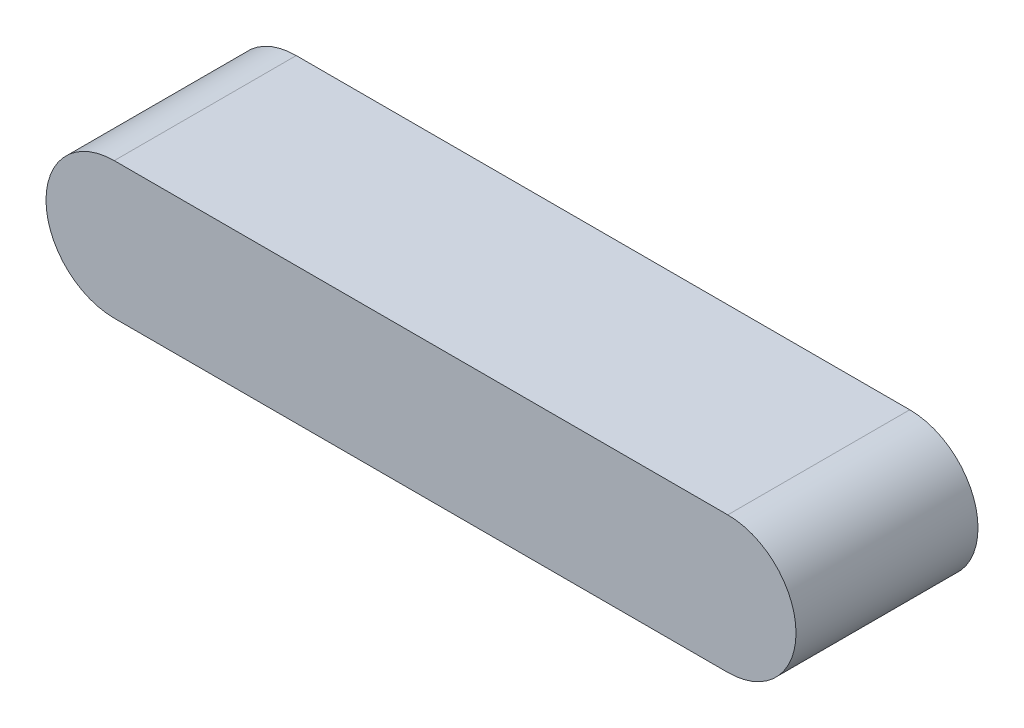
SolidWorks part; units mm, degrees
ref_plane "前视基准面" through (0, 0, 0) normal (0, 0, 1) x (1, 0, 0)
ref_plane "上视基准面" through (0, 0, 0) normal (0, 1, 0) x (1, 0, 0)
ref_plane "右视基准面" through (0, 0, 0) normal (1, 0, 0) x (0, 0, -1)
sketch "草图1" plane through (0, 0, 0) normal (0, 0, 1) x (1, 0, 0)
  line L0 (-64.7, 0) -> (70.15, 0) construction
  line L1 (-64.7, 15) -> (70.15, 15)
  line L2 (-64.7, -15) -> (70.15, -15)
  arc A0 (-64.7, 15) -> (-64.7, -15) centre (-64.7, 0) ccw
  arc A1 (70.15, -15) -> (70.15, 15) centre (70.15, 0) ccw
  point P3 (2.725, 0)
  point P8 (-79.7, 0)
  point P9 (85.15, 0)
  dimension "D1" = 164.85
  dimension "D2" = 30
  dimension "D3" = 64.7
extrude "凸台-拉伸1" add sketch "草图1" along normal blind 40
sketch "草图2" plane through (0, 0, 0) normal (0, 0, -1) x (-1, 0, 0)
  circle A0 centre (-37.5, 0) radius 7.25
  dimension "D1" = 14.5
  dimension "D2" = 37.5
extrude "切除-拉伸1" cut sketch "草图2" against normal blind 1
chamfer "倒角1" distance 0.5 angle 45 2 edges at (30.25, 0, 0) (30.25, 0, 1)
sketch "草图5" plane through (0, 0, 1) normal (0, 0, -1) x (-1, 0, 0)
  circle A0 centre (-37.5, 0) radius 5.5
  dimension "D1" = 11
extrude "切除-拉伸2" cut sketch "草图5" against normal blind 1
chamfer "倒角2" distance 0.5 angle 30 1 edges at (32, 0, 1)
sketch "草图6" plane through (0, 0, 2) normal (0, 0, -1) x (-1, 0, 0)
  circle A0 centre (-37.5, 0) radius 4.5
  dimension "D1" = 9
extrude "切除-拉伸3" cut sketch "草图6" against normal blind 1
chamfer "倒角3" distance 0.5 angle 60 1 edges at (33, 0, 2)
sketch "草图7" plane through (0, 0, 3) normal (0, 0, -1) x (-1, 0, 0)
  circle A0 centre (-37.5, 0) radius 2.5
  dimension "D1" = 5
extrude "切除-拉伸4" cut sketch "草图7" against normal blind 1
chamfer "倒角4" distance 0.5 angle 60 1 edges at (35, 0, 3)
mirror "镜向3" about plane through (0, 0, 0) normal (1, 0, 0) of "切除-拉伸1", "倒角1", "切除-拉伸2", "倒角2", "切除-拉伸3", "倒角3", "切除-拉伸4", "倒角4"
sketch "草图9" plane through (0, 0, 0) normal (0, 0, -1) x (-1, 0, 0)
  circle A0 centre (12.5, 0) radius 7.25
  dimension "D1" = 14.5
  dimension "D2" = 12.5
extrude "切除-拉伸5" cut sketch "草图9" against normal blind 1
chamfer "倒角5" distance 0.5 angle 45 1 edges at (-19.75, 0, 1)
sketch "草图10" plane through (0, 0, 1) normal (0, 0, -1) x (-1, 0, 0)
  circle A0 centre (12.5, 0) radius 5.6
  dimension "D1" = 11.2
extrude "切除-拉伸6" cut sketch "草图10" against normal blind 1
chamfer "倒角6" distance 0.5 angle 60 1 edges at (-18.1, 0, 1)
sketch "草图11" plane through (0, 0, 2) normal (0, 0, -1) x (-1, 0, 0)
  circle A0 centre (12.5, 0) radius 4.35
  dimension "D1" = 8.7
extrude "切除-拉伸7" cut sketch "草图11" against normal blind 1
chamfer "倒角7" distance 0.5 angle 60 1 edges at (-16.85, 0, 2)
sketch "草图12" plane through (0, 0, 3) normal (0, 0, -1) x (-1, 0, 0)
  circle A0 centre (12.5, 0) radius 3
  dimension "D1" = 6
extrude "切除-拉伸8" cut sketch "草图12" against normal blind 1
chamfer "倒角8" distance 0.5 angle 60 1 edges at (-15.5, 0, 4)
sketch "草图13" plane through (0, 0, 0) normal (0, 0, -1) x (-1, 0, 0)
  line L0 (-70.2498, 0) -> (64.6854, 0) construction
  line L1 (-70.2498, 12.9899) -> (64.6854, 12.9899)
  line L2 (-70.2498, -12.9899) -> (64.6854, -12.9899)
  arc A0 (-70.2498, 12.9899) -> (-70.2498, -12.9899) centre (-70.2498, 0) ccw
  arc A1 (64.6854, -12.9899) -> (64.6854, 12.9899) centre (64.6854, 0) ccw
  point P3 (-2.7822, 0)
extrude "切除-拉伸9" cut sketch "草图13" against normal blind 1.5
fillet "圆角1" radius 1 4 edges at (2.7822, 12.9899, 1.5) (-77.6753, 0, 1.5) (2.7822, -12.9899, 1.5) (83.2397, 0, 1.5)
sketch "草图14" plane through (0, 0, 1.5) normal (0, 0, -1) x (-1, 0, 0)
  line L0 (-24.5, 4.5) -> (-37.5, 4.5) construction
  line L1 (-37.5, 4.5) -> (-37.5, 0) construction
  circle A0 centre (-24.5, 4.5) radius 2
  dimension "D1" = 4
  dimension "D2" = 13
  dimension "D3" = 4.5
extrude "切除-拉伸10" cut sketch "草图14" against normal blind 1
fillet "圆角2" radius 0.6 1 edges at (22.5, 4.5, 2.5)
sketch "草图15" plane through (0, 0, 1.5) normal (0, 0, -1) x (-1, 0, 0)
  line L0 (-24.5, 4.5) -> (-24.5, -4.5) construction
  line L1 (-37.5, 0) -> (-37.5, -4.5) construction
  line L2 (-37.5, -4.5) -> (-24.5, -4.5) construction
  circle A0 centre (-24.5, -4.5) radius 2
  dimension "D1" = 4
  dimension "D2" = 4.5
extrude "切除-拉伸11" cut sketch "草图15" against normal blind 1
fillet "圆角3" radius 0.6 1 edges at (22.5, -4.5, 2.5)
sketch "草图16" plane through (0, 0, 1.5) normal (0, 0, -1) x (-1, 0, 0)
  line L0 (-60.5, 0) -> (-37.5, 0) construction
  arc A0 (-59.7791, -0.6802) -> (-59.8198, 0.7209) centre (-59.7995, 0.0204) cw construction
  arc A1 (-59.8313, 1.1147) -> (-59.7676, -1.074) centre (-59.7995, 0.0204) ccw
  arc A2 (-59.8084, 0.3271) -> (-59.7906, -0.2863) centre (-59.7995, 0.0204) ccw
  arc A3 (-59.8084, 0.3271) -> (-59.8313, 1.1147) centre (-59.8198, 0.7209) ccw
  arc A4 (-59.7676, -1.074) -> (-59.7906, -0.2863) centre (-59.7791, -0.6802) ccw
  point P3 (-60.5, 0)
  dimension "D1" = 23
extrude "切除-拉伸12" cut sketch "草图16" against normal blind 3
mirror "镜向6" about plane through (0, 0, 0) normal (1, 0, 0) of "切除-拉伸12"
sketch "草图17" plane through (0, -15, 0) normal (0, -1, 0) x (1, 0, 0)
  line L0 (0, 0) -> (0, 44.0548) construction
  line L1 (-64.7, 0) -> (70.15, 0) construction
  line L2 (-13, 7) -> (13, 7)
  line L3 (-13, 7) -> (-13, 14)
  line L4 (-13, 14) -> (13, 14)
  line L5 (13, 7) -> (13, 14)
  line L6 (-13, 7) -> (13, 14) construction
  line L11 (-13, 14) -> (13, 7) construction
  point P2 (0, 10.5)
  dimension "D1" = 26
  dimension "D2" = 7
  dimension "D3" = 7
extrude "凸台-拉伸2" add sketch "草图17" along normal blind 6.5
sketch "草图18" plane through (0, -21.5, 0) normal (0, -1, 0) x (1, 0, 0)
  line L0 (-13, 13) -> (-6.5, 13)
  line L1 (-13, 14) -> (-13, 7) construction
  line L2 (-6.5, 13) -> (-6.5, 8)
  line L3 (-6.5, 8) -> (-13, 8)
  line L4 (-13, 14) -> (-13, 7) construction
  line L5 (-13, 8) -> (-13, 13)
  line L6 (-13, 7) -> (13, 7) construction
  line L7 (13, 13) -> (6.5, 13)
  line L8 (13, 7) -> (13, 14) construction
  line L9 (6.5, 13) -> (6.5, 8)
  line L10 (6.5, 8) -> (13, 8)
  line L11 (13, 7) -> (13, 14) construction
  line L12 (13, 8) -> (13, 13)
  line L13 (-5.5, 13) -> (-5.5, 8)
  line L14 (-5.5, 8) -> (-0.5, 8)
  line L15 (-0.5, 8) -> (-0.5, 13)
  line L16 (-0.5, 13) -> (-5.5, 13)
  line L17 (0.5, 13) -> (0.5, 8)
  line L18 (0.5, 8) -> (5.5, 8)
  line L19 (5.5, 8) -> (5.5, 13)
  line L20 (5.5, 13) -> (0.5, 13)
  dimension "D1" = 5
  dimension "D2" = 1
  dimension "D3" = 6.5
  dimension "D4" = 6.5
  dimension "D5" = 5
  dimension "D6" = 1
  dimension "D7" = 1
  dimension "D8" = 1
extrude "切除-拉伸13" cut sketch "草图18" against normal blind 3
sketch "草图19" plane through (0, -18.5, 0) normal (0, -1, 0) x (1, 0, 0)
  line L0 (-64.7, 0) -> (70.15, 0) construction
  line L1 (13, 8) -> (13, 13) construction
  line L2 (-9.7, 11) -> (9, 11) construction
  circle A0 centre (9, 11) radius 1.25
  circle A1 centre (-9.7, 11) radius 1.25
  dimension "D1" = 11
  dimension "D3" = 2.5
  dimension "D4" = 2.5
  dimension "D2" = 4
  dimension "D5" = 18.7
extrude "切除-拉伸14" cut sketch "草图19" against normal blind 3
sketch "草图20" plane through (0, -15, 0) normal (0, -1, 0) x (1, 0, 0)
  line L0 (0, 0) -> (0, 27.4652) construction
  line L6 (-17.5, 3.5) -> (17.5, 3.5) construction
  line L7 (-9.7, 11) -> (9, 11) construction
  line L8 (-17.5, 3.5) -> (-17.5, 18.5) construction
  line L9 (-17.5, 18.5) -> (17.5, 18.5) construction
  line L10 (17.5, 3.5) -> (17.5, 18.5) construction
  line L11 (-17.5, 3.5) -> (17.5, 18.5) construction
  line L12 (-17.5, 18.5) -> (17.5, 3.5) construction
  point P1 (0, 11)
  point P10 (0, 0)
  dimension "D1" = 35
  dimension "D2" = 15
